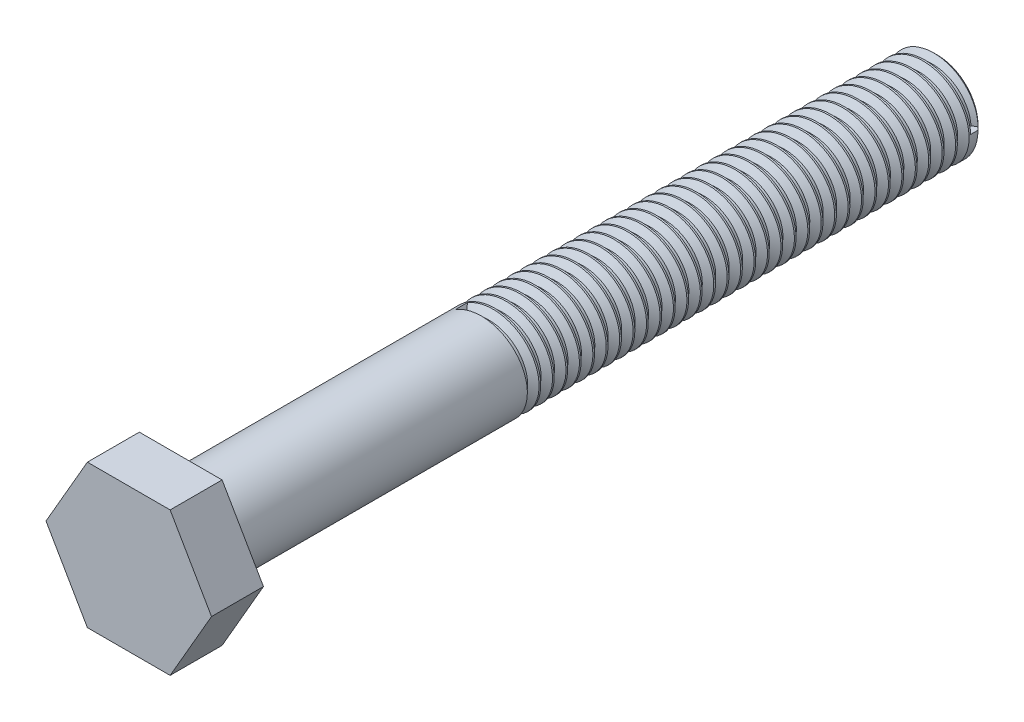
SolidWorks part; units mm, degrees
material "AISI 1018"
ref_plane "Front Plane" through (0, 0, 0) normal (0, 0, 1) x (1, 0, 0)
ref_plane "Top Plane" through (0, 0, 0) normal (0, 1, 0) x (1, 0, 0)
ref_plane "Right Plane" through (0, 0, 0) normal (1, 0, 0) x (0, 0, -1)
ref_plane "Plane1"
sketch "Sketch1" plane through (0, 0, 0) normal (0, 0, 1) x (1, 0, 0)
  line L0 (6.9282, -4) -> (4.6188, -8)
  line L1 (4.6188, -8) -> (0, -8)
  line L2 (0, -8) -> (-4.6188, -8)
  line L3 (-4.6188, -8) -> (-6.9282, -4)
  line L4 (-6.9282, -4) -> (-9.2376, 0)
  line L5 (-9.2376, 0) -> (-6.9282, 4)
  line L6 (-6.9282, 4) -> (-4.6188, 8)
  line L7 (-4.6188, 8) -> (0, 8)
  line L8 (0, 8) -> (4.6188, 8)
  line L9 (4.6188, 8) -> (6.9282, 4)
  line L10 (6.9282, 4) -> (9.2376, 0)
  line L11 (9.2376, 0) -> (6.9282, -4)
extrude "Extrusion1" add sketch "Sketch1" against normal blind 5.8
sketch "Sketch2" plane through (0, 0, -5.8) normal (0, 0, -1) x (-1, 0, 0)
  circle A0 centre (0, 0) radius 5
  dimension "D1" = 10
extrude "Boss-Extrude4" add sketch "Sketch2" along normal blind 34.5 contours A0
sketch "Sketch6" plane through (0, 0, -40.3) normal (0, 0, -1) x (-1, 0, 0)
  circle A2 centre (0, 0) radius 5
  circle A3 centre (0, 0) radius 5
  dimension "D1" = 0
extrude "Boss-Extrude5" add sketch "Sketch6" along normal blind 50
thread "Thread2" pitch 1.5 method cut profile "Thread Profile4" start angle 0, offset 0, length 50, pitch 1.5, diameter 10
ref_plane "Plane5" through (5, 0, -90.3) normal (0, -1, 0) x (1, 0, 0)
sketch "Thread Profile4" plane through (5, 0, -90.3) normal (0, -1, 0) x (1, 0, 0)
  line L0 (0, 0) -> (0, 1.5) construction
  line L11 (0, 0) -> (0, 1.3125)
  line L12 (0, 1.3125) -> (-0.8119, 0.8437)
  line L13 (-0.8119, 0.8437) -> (-0.8119, 0.4687)
  line L15 (-0.8119, 0.4687) -> (0, 0)
  line L17 (-0.8119, 0.6562) -> (0, 0.6562) construction
  point P2 (0, 0)
  dimension "Pitch" = 1.5
  dimension "Profile_Angle" = 60
  dimension "Profile_Land" = 0.375
  dimension "Profile_Height" = 0.8119
chamfer "Chamfer2" distance 0.5 angle 45 1 edges at (-5, 0, -90.3)
